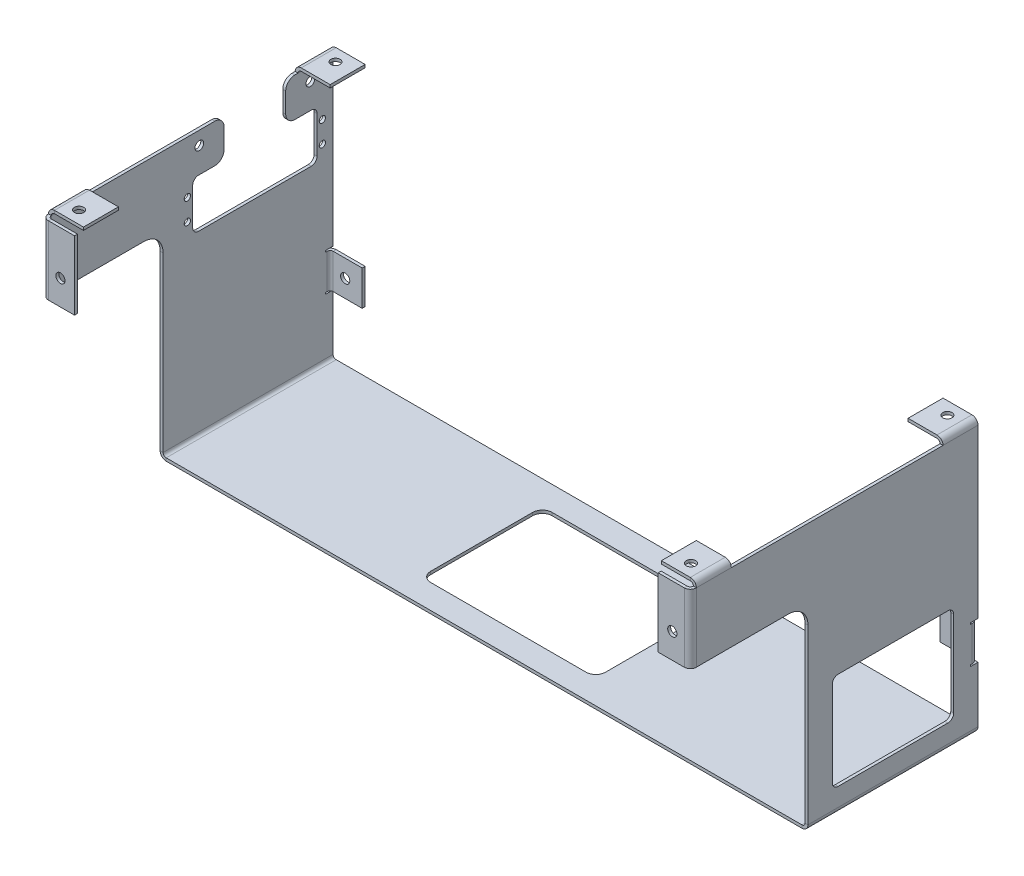
SolidWorks part; units mm, degrees
note: The reader was unsure of these and kept them because the rebuilt part matched: flange length of "Edge-Flange2", "Edge-Flange3", "Edge-Flange6", "Edge-Flange7", "Edge-Flange8".
material "Low Carbon Steel"
ref_plane "Front Plane" through (0, 0, 0) normal (0, 0, 1) x (1, 0, 0)
ref_plane "Top Plane" through (0, 0, 0) normal (0, 1, 0) x (1, 0, 0)
ref_plane "Right Plane" through (0, 0, 0) normal (1, 0, 0) x (0, 0, -1)
sketch "Sketch1" plane through (0, 0, 0) normal (1, 0, 0) x (0, 0, -1)
  line L0 (-175, 198) -> (-290, 198)
  line L1 (0, 0) -> (-175, 0)
  line L2 (0, 0) -> (0, 275)
  line L3 (0, 275) -> (-290, 275)
  line L4 (-175, 0) -> (-175, 198)
  line L5 (-290, 198) -> (-290, 275)
  dimension "D1" = 275
  dimension "D2" = 175
  dimension "D3" = 115
  dimension "D4" = 77
base flange "Base-Flange1" sketch "Sketch1" thickness 3.0378 reverse thickness direction no parameters "D1"=3.175
edge flange "Edge-Flange2" sketch "Sketch16" flange angle 90 flange length 667 flange position bend outside bend radius 3.175 thickness 3.0378 relief rectangular parameters "D6"=10
sketch "Sketch16" plane through (0, 0, 0) normal (0, -1, 0) x (0, 0, -1)
  line L0 (-175, 0) -> (0, 0) construction
  line L1 (-175, 0) -> (0, 0)
  line L2 (-175, 0) -> (-175, 663.9622)
  line L3 (-175, 663.9622) -> (0, 663.9622)
  line L4 (0, 663.9622) -> (0, 0)
bend "EdgeBend3" bend radius 3.175 bend angle 90 parameters "D5"=3
edge flange "Edge-Flange3" sketch "Sketch19" flange angle 90 flange length 281.2128 flange position material inside bend radius 3.175 thickness 3.0378 relief rectangular parameters "D6"=10
sketch "Sketch19" plane through (663.9622, -3.175, 0) normal (1, 0, 0) x (0, 0, -1)
  line L0 (0, 0) -> (-175, 0) construction
  line L1 (0, 0) -> (-175, 0)
  line L2 (-175, 0) -> (-175, 201.175)
  line L3 (-290, 278.175) -> (0, 278.175)
  line L4 (0, 278.175) -> (0, 0)
  line L5 (-175, 201.175) -> (-290, 201.175)
  line L6 (-290, 201.175) -> (-290, 278.175)
  line L7 (0, 278.175) -> (-290, 278.175) construction
  line L8 (-290, 278.175) -> (-290, 201.175) construction
bend "EdgeBend4" bend radius 3.175 bend angle 90 parameters "D5"=4
fillet "Fillet1" radius 20 2 edges at (-1.5189, 198, 175) (662.4432, 198, 175)
edge flange "Edge-Flange6" sketch "Sketch36" flange profiles "Sketch36", "Sketch37" flange angle 90 flange length 36 flange position material inside bend radius 3.175 thickness 3.0378 relief rectangular parameters "D6"=10, "D8"=1
sketch "Sketch36" plane through (0, 275, 0) normal (0, 1, 0) x (0, 0, 1)
  line L0 (0, 0) -> (290, 0) construction
  line L1 (0, 0) -> (290, 0)
  line L2 (0, 0) -> (0, 32.9622)
  line L3 (0, 32.9622) -> (290, 32.9622)
  line L4 (290, 32.9622) -> (290, 0)
sketch "Sketch37" plane through (660.9243, 275, 0) normal (0, 1, 0) x (0, 0, -1)
  line L0 (0, 0) -> (-290, 0) construction
  line L1 (0, 0) -> (-290, 0)
  line L2 (-290, 0) -> (-290, 32.9622)
  line L3 (-290, 32.9622) -> (0, 32.9622)
  line L4 (0, 32.9622) -> (0, 0)
bend "EdgeBend9" bend radius 3.175 bend angle 90 parameters "D5"=5
bend "EdgeBend10" bend radius 3.175 bend angle 90 parameters "D5"=6
sketch "Sketch38" plane through (663.9622, 0, 0) normal (1, 0, 0) x (0, 0, -1)
  line L0 (0, 268.7872) -> (-290, 268.7872) construction
  line L1 (-254, 268.7872) -> (-36, 268.7872)
  line L2 (-254, 268.7872) -> (-254, 275)
  line L3 (-254, 275) -> (-36, 275)
  line L4 (-36, 268.7872) -> (-36, 275)
  line L5 (0, 275) -> (-290, 275) construction
  line L7 (-290, 268.7872) -> (-290, 198) construction
  line L8 (0, 0) -> (0, 268.7872) construction
  dimension "D1" = 36
  dimension "D2" = 36
extrude "Cut-Extrude1" cut sketch "Sketch38" against normal through all
edge flange "Edge-Flange7" sketch "Sketch43" flange profiles "Sketch43", "Sketch44" flange angle 90 flange length 36 flange position material inside bend radius 3.175 thickness 3.0378 relief rectangular parameters "D6"=10, "D8"=1
sketch "Sketch43" plane through (0, 0, 0) normal (0, 0, -1) x (0, 1, 0)
  line L0 (0, 0) -> (268.7872, 0) construction
  line L1 (59, 0) -> (95, 0)
  line L2 (59, 0) -> (59, 32.9622)
  line L3 (59, 32.9622) -> (95, 32.9622)
  line L4 (95, 32.9622) -> (95, 0)
  line L5 (275, 32.9622) -> (275, 3.175) construction
  dimension "D1" = 36
  dimension "D2" = 180
sketch "Sketch44" plane through (660.9243, 0, 0) normal (0, 0, -1) x (0, -1, 0)
  line L0 (0, 0) -> (-268.7872, 0) construction
  line L1 (-59, 0) -> (-95, 0)
  line L2 (-95, 0) -> (-95, 32.9622)
  line L3 (-95, 32.9622) -> (-59, 32.9622)
  line L4 (-59, 32.9622) -> (-59, 0)
  line L5 (-95, 627.9622) -> (-95, 660.9243) construction
  line L6 (-59, 660.9243) -> (-59, 627.9622) construction
bend "EdgeBend11" bend radius 3.175 bend angle 90 parameters "D5"=7
bend "EdgeBend12" bend radius 3.175 bend angle 90 parameters "D5"=8
edge flange "Edge-Flange8" sketch "Sketch57" flange profiles "Sketch57", "Sketch58" flange angle 90 flange length 33 flange position bend outside bend radius 3.175 thickness 3.0378 relief rectangular parameters "D6"=10, "D8"=1
sketch "Sketch57" plane through (0, 0, 290) normal (0, 0, 1) x (0, -1, 0)
  line L2 (-268.7872, 0) -> (-268.7872, 29.9622)
  line L3 (-268.7872, 29.9622) -> (-198, 29.9622)
  line L4 (-198, 29.9622) -> (-198, 0)
  line L7 (-268.7872, 0) -> (-198, 0) construction
  line L8 (-268.7872, 0) -> (-198, 0)
sketch "Sketch58" plane through (660.9243, 0, 290) normal (0, 0, 1) x (0, 1, 0)
  line L0 (268.7872, 0) -> (198, 0) construction
  line L1 (268.7872, 0) -> (198, 0)
  line L2 (198, 0) -> (198, 29.9622)
  line L3 (198, 29.9622) -> (268.7872, 29.9622)
  line L4 (268.7872, 29.9622) -> (268.7872, 0)
bend "EdgeBend13" bend radius 3.175 bend angle 90 parameters "D5"=9
bend "EdgeBend14" bend radius 3.175 bend angle 90 parameters "D5"=10
hole_wizard "Ø9.5 (9.5) Diameter Hole1" positions "Sketch45" profile "Sketch46" hole size "Ø9.5" standard "Peddi DIN" end condition up to next
sketch "Sketch45" plane through (0, 275, 0) normal (0, 1, 0) x (1, 0, 0)
  line L0 (645.4622, -13) -> (645.4622, -277) construction
  line L1 (645.4622, -277) -> (15.4622, -277) construction
  line L2 (15.4622, -277) -> (15.4622, -13) construction
  line L3 (15.4622, -13) -> (645.4622, -13) construction
  line L5 (330.4622, 0) -> (330.4622, -13) construction
  line L6 (3.175, 0) -> (657.7493, 0) construction
  line L8 (32.9622, -36) -> (32.9622, -254) construction
  line L10 (32.9622, -145) -> (15.4622, -145) construction
  point P0 (15.4622, -13)
  point P2 (15.4622, -277)
  point P4 (645.4622, -277)
  point P6 (645.4622, -13)
  dimension "D1" = 630
  dimension "D2" = 264
sketch "Sketch46" plane through (15.4622, 275, 13) normal (1, 0, 0) x (0, 0, 1)
  line L0 (0, 0) -> (0, 3.0378)
  line L1 (0, 3.0378) -> (4.75, 3.0378)
  line L2 (4.75, 3.0378) -> (4.75, 0)
  line L5 (4.75, 0) -> (0, 0)
  line L11 (0, -6.35) -> (0, 107.95) construction
  dimension "Thru Hole Dia." = 9.5
  dimension "Thru Hole Depth" = 3.0378
hole_wizard "Ø9.5 (9.5) Diameter Hole2" positions "Sketch47" profile "Sketch48" hole size "Ø9.5" standard "Peddi DIN" end condition up to next
sketch "Sketch47" plane through (0, 0, 0) normal (0, 0, -1) x (-1, 0, 0)
  line L0 (-15.4622, 77) -> (-645.4622, 77) construction
  line L2 (-330.4622, -3.175) -> (-330.4622, 77) construction
  line L3 (-3.175, -3.175) -> (-657.7493, -3.175) construction
  line L5 (-32.9622, 275) -> (-3.175, 275) construction
  point P0 (-645.4622, 77)
  point P2 (-15.4622, 77)
  dimension "D1" = 630
  dimension "D2" = 198
sketch "Sketch48" plane through (645.4622, 77, 0) normal (1, 0, 0) x (0, 1, 0)
  line L0 (0, 0) -> (0, 3.0378)
  line L1 (0, 3.0378) -> (4.75, 3.0378)
  line L2 (4.75, 3.0378) -> (4.75, 0)
  line L5 (4.75, 0) -> (0, 0)
  line L11 (0, -6.35) -> (0, 107.95) construction
  dimension "Thru Hole Dia." = 9.5
  dimension "Thru Hole Depth" = 3.0378
sketch "Sketch49" plane through (660.9243, 0, 0) normal (-1, 0, 0) x (0, 0, 1)
  line L0 (175, 178) -> (175, 0) construction
  line L1 (144, 118.7872) -> (31, 118.7872)
  line L2 (150, 112.7872) -> (150, 24.7872)
  line L3 (144, 18.7872) -> (31, 18.7872)
  line L4 (25, 112.7872) -> (25, 24.7872)
  line L5 (0, 96.5189) -> (0, 268.7872) construction
  line L6 (0, -6.2128) -> (175, -6.2128) construction
  arc A0 (31, 18.7872) -> (25, 24.7872) centre (31, 24.7872) cw
  arc A1 (150, 24.7872) -> (144, 18.7872) centre (144, 24.7872) cw
  arc A2 (144, 118.7872) -> (150, 112.7872) centre (144, 112.7872) cw
  arc A3 (31, 118.7872) -> (25, 112.7872) centre (31, 112.7872) ccw
  dimension "D6" = 6
  dimension "D1" = 125
  dimension "D2" = 100
  dimension "D3" = 25
  dimension "D4" = 25
  dimension "D5" = 25
extrude "Cut-Extrude2" cut sketch "Sketch49" against normal through all
hole_wizard "M5 Clearance Hole1" positions "Sketch50" profile "Sketch51" hole size "M5" standard "Peddi DIN" end condition up to next
sketch "Sketch50" plane through (-3.0378, 0, 0) normal (-1, 0, 0) x (0, 0, 1)
  line L0 (11.05, 215) -> (150.05, 215) construction
  line L1 (150.05, 215) -> (150.05, 193) construction
  line L2 (150.05, 193) -> (11.05, 193) construction
  line L3 (11.05, 193) -> (11.05, 215) construction
  line L6 (0, 95) -> (0, 59) construction
  line L7 (36, 275) -> (0, 275) construction
  point P0 (11.05, 215)
  point P2 (11.05, 193)
  point P4 (150.05, 215)
  point P6 (150.05, 193)
  dimension "D1" = 139
  dimension "D2" = 22
  dimension "D3" = 60
  dimension "D4" = 11.05
sketch "Sketch51" plane through (-3.0378, 215, 11.05) normal (0, 1, 0) x (0, 0, 1)
  line L0 (0, 0) -> (0, 3.0378)
  line L1 (0, 3.0378) -> (3.25, 3.0378)
  line L2 (3.25, 3.0378) -> (3.25, 0)
  line L5 (3.25, 0) -> (0, 0)
  line L11 (0, -6.35) -> (0, 107.95) construction
  dimension "Thru Hole Dia." = 6.5
  dimension "Thru Hole Depth" = 3.0378
sketch "Sketch52" plane through (-3.0378, 0, 0) normal (-1, 0, 0) x (0, 0, 1)
  line L0 (11.05, 215) -> (11.05, 193) construction
  line L1 (22.55, 229) -> (138.55, 229)
  line L2 (16.55, 223) -> (16.55, 185)
  line L3 (22.55, 179) -> (138.55, 179)
  line L4 (144.55, 223) -> (144.55, 185)
  line L5 (16.55, 204) -> (11.05, 204) construction
  line L6 (150.05, 215) -> (150.05, 193) construction
  line L7 (150.05, 204) -> (144.55, 204) construction
  arc A0 (138.55, 229) -> (144.55, 223) centre (138.55, 223) cw
  arc A1 (138.55, 179) -> (144.55, 185) centre (138.55, 185) ccw
  arc A2 (16.55, 185) -> (22.55, 179) centre (22.55, 185) ccw
  arc A3 (22.55, 229) -> (16.55, 223) centre (22.55, 223) ccw
  dimension "D3" = 6
  dimension "D1" = 50
  dimension "D2" = 128
extrude "Cut-Extrude3" cut sketch "Sketch52" against normal up to next
hole_wizard "Ø9.5 (9.5) Diameter Hole3" positions "Sketch59" profile "Sketch60" hole size "Ø9.5" standard "Peddi DIN" end condition up to next
sketch "Sketch59" plane through (0, 0, 296.2128) normal (0, 0, 1) x (1, 0, 0)
  line L0 (15.4622, 223.7872) -> (645.4622, 223.7872) construction
  line L2 (657.7493, -6.2128) -> (3.175, -6.2128) construction
  line L3 (330.4622, 223.7872) -> (330.4622, -6.2128) construction
  point P0 (645.4622, 223.7872)
  point P2 (15.4622, 223.7872)
  dimension "D1" = 230
  dimension "D2" = 630
sketch "Sketch60" plane through (645.4622, 223.7872, 296.2128) normal (1, 0, 0) x (0, -1, 0)
  line L0 (0, 0) -> (0, 3.0378)
  line L1 (0, 3.0378) -> (4.75, 3.0378)
  line L2 (4.75, 3.0378) -> (4.75, 0)
  line L5 (4.75, 0) -> (0, 0)
  line L11 (0, -6.35) -> (0, 107.95) construction
  dimension "Thru Hole Dia." = 9.5
  dimension "Thru Hole Depth" = 3.0378
sketch "Sketch61" plane through (0, -3.175, 0) normal (0, 1, 0) x (1, 0, 0)
  line L0 (3.175, 0) -> (657.7493, 0) construction
  line L1 (250.4622, -25) -> (410.4622, -25)
  line L2 (240.4622, -35) -> (240.4622, -140)
  line L3 (250.4622, -150) -> (410.4622, -150)
  line L4 (420.4622, -35) -> (420.4622, -140)
  line L9 (657.7493, -175) -> (3.175, -175) construction
  line L12 (330.4622, -150) -> (330.4622, -175) construction
  arc A4 (410.4622, -150) -> (420.4622, -140) centre (410.4622, -140) ccw
  arc A5 (240.4622, -140) -> (250.4622, -150) centre (250.4622, -140) ccw
  arc A6 (250.4622, -25) -> (240.4622, -35) centre (250.4622, -35) ccw
  arc A7 (410.4622, -25) -> (420.4622, -35) centre (410.4622, -35) cw
  dimension "D5" = 10
  dimension "D1" = 180
  dimension "D2" = 25
  dimension "D3" = 25
  dimension "D4" = 125
extrude "Cut-Extrude4" cut sketch "Sketch61" against normal through all
sketch "Sketch62" plane through (-3.0378, 0, 0) normal (-1, 0, 0) x (0, 0, 1)
  line L0 (254, 268.7872) -> (36, 268.7872) construction
  line L1 (48.8, 268.7872) -> (112.3, 268.7872)
  line L2 (48.8, 268.7872) -> (48.8, 229)
  line L3 (48.8, 229) -> (112.3, 229)
  line L4 (112.3, 268.7872) -> (112.3, 229)
  line L5 (138.55, 229) -> (22.55, 229) construction
  line L6 (80.55, 179) -> (80.55, 229) construction
  line L7 (22.55, 179) -> (138.55, 179) construction
  dimension "D1" = 63.5
extrude "Cut-Extrude5" cut sketch "Sketch62" against normal up to next normal cut yes
fillet "Fillet2" radius 9.525 4 edges at (-1.5189, 268.7872, 112.3) (-1.5189, 229, 112.3) (-1.5189, 229, 48.8) (-1.5189, 268.7872, 48.8)
hole_wizard "M8 Clearance Hole1" positions "Sketch63" profile "Sketch64" hole size "M8" standard "Peddi DIN" end condition up to next
sketch "Sketch63" plane through (-3.0378, 0, 0) normal (-1, 0, 0) x (0, 0, 1)
  circle A0 centre (11.05, 215) radius 3.25 construction
  point P0 (23.4, 255.05)
  point P2 (137.7, 255.05)
  dimension "D1" = 114.3
  dimension "D2" = 12.35
  dimension "D3" = 40.05
sketch "Sketch64" plane through (-3.0378, 255.05, 23.4) normal (0, 1, 0) x (0, 0, 1)
  line L0 (0, 0) -> (0, 3.0378)
  line L1 (0, 3.0378) -> (4.5, 3.0378)
  line L2 (4.5, 3.0378) -> (4.5, 0)
  line L5 (4.5, 0) -> (0, 0)
  line L11 (0, -6.35) -> (0, 107.95) construction
  dimension "Thru Hole Dia." = 9
  dimension "Thru Hole Depth" = 3.0378
other "Freeze***"
sketch "Bend-Lines1" [suppressed] plane through (0, 0, 0) normal (0, 1, 0) x (1, 0, 0)
sketch "Bounding-Box1" [suppressed] plane through (0, 0, 0) normal (0, 1, 0) x (1, 0, 0)
sheet metal parameters "Sheet-Metal1" thickness 3.0378 parameters "D1"=3.175
flat pattern "Flat-Pattern1" [suppressed]
sketch "Bend-Lines2" plane through (0, 0, 0) normal (0, 1, 0) x (1, 0, 0)
sketch "Bounding-Box2" [suppressed] plane through (0, 0, 0) normal (0, 1, 0) x (1, 0, 0)
sheet metal parameters "Sheet-Metal3" thickness 3.0378 parameters "D1"=3.175
flat pattern "Flat-Pattern1" [suppressed]
sketch "Bend-Lines2"
sketch "Bounding-Box2" [suppressed] plane through (0, 0, 0) normal (0, 1, 0) x (1, 0, 0)
bend of the flat pattern "Flatten-<EdgeBend3>1"
sheet metal parameters "Sheet-Metal4" thickness 3.0378 parameters "D1"=3.175
flat pattern "Flat-Pattern1" [suppressed]
sketch "Bend-Lines2" plane through (0, 0, 0) normal (0, 1, 0) x (1, 0, 0)
sketch "Bounding-Box2" [suppressed] plane through (0, 0, 0) normal (0, 1, 0) x (1, 0, 0)
bend of the flat pattern "Flatten-<EdgeBend3>1"
bend of the flat pattern "Flatten-<EdgeBend4>1"
sheet metal parameters "Sheet-Metal7" thickness 3.0378 parameters "D1"=3.175
flat pattern "Flat-Pattern1" [suppressed]
sketch "Bend-Lines2" plane through (0, 0, 0) normal (0, 1, 0) x (1, 0, 0)
sketch "Bounding-Box2" [suppressed] plane through (0, 0, 0) normal (0, 1, 0) x (1, 0, 0)
bend of the flat pattern "Flatten-<EdgeBend3>1"
bend of the flat pattern "Flatten-<EdgeBend4>1"
bend of the flat pattern "Flatten-<EdgeBend9>1"
bend of the flat pattern "Flatten-<EdgeBend10>1"
sheet metal parameters "Sheet-Metal8" thickness 3.0378 parameters "D1"=3.175
flat pattern "Flat-Pattern1" [suppressed]
sketch "Bend-Lines2" plane through (0, 0, 0) normal (0, 1, 0) x (1, 0, 0)
sketch "Bounding-Box2" [suppressed] plane through (0, 0, 0) normal (0, 1, 0) x (1, 0, 0)
bend of the flat pattern "Flatten-<EdgeBend3>1"
bend of the flat pattern "Flatten-<EdgeBend4>1"
bend of the flat pattern "Flatten-<EdgeBend9>1"
bend of the flat pattern "Flatten-<EdgeBend10>1"
sheet metal parameters "Sheet-Metal9" thickness 3.0378 parameters "D1"=3.175
flat pattern "Flat-Pattern1" [suppressed]
sketch "Bend-Lines2" plane through (0, 0, 0) normal (0, 1, 0) x (1, 0, 0)
sketch "Bounding-Box2" [suppressed] plane through (0, 0, 0) normal (0, 1, 0) x (1, 0, 0)
bend of the flat pattern "Flatten-<EdgeBend3>1"
bend of the flat pattern "Flatten-<EdgeBend4>1"
bend of the flat pattern "Flatten-<EdgeBend9>1"
bend of the flat pattern "Flatten-<EdgeBend10>1"
bend of the flat pattern "Flatten-<EdgeBend11>1"
bend of the flat pattern "Flatten-<EdgeBend12>1"
sheet metal parameters "Sheet-Metal10" thickness 3.0378 parameters "D1"=3.175
flat pattern "Flat-Pattern1" [suppressed]
sketch "Bend-Lines2" plane through (0, 0, 0) normal (0, 1, 0) x (1, 0, 0)
sketch "Bounding-Box2" [suppressed] plane through (0, 0, 0) normal (0, 1, 0) x (1, 0, 0)
bend of the flat pattern "Flatten-<EdgeBend3>1"
bend of the flat pattern "Flatten-<EdgeBend4>1"
bend of the flat pattern "Flatten-<EdgeBend9>1"
bend of the flat pattern "Flatten-<EdgeBend10>1"
bend of the flat pattern "Flatten-<EdgeBend11>1"
bend of the flat pattern "Flatten-<EdgeBend12>1"
bend of the flat pattern "Flatten-<EdgeBend13>2"
bend of the flat pattern "Flatten-<EdgeBend14>2"
sheet metal parameters "Sheet-Metal11" thickness 3.0378 parameters "D1"=3.175
flat pattern "Flat-Pattern1" [suppressed]
sketch "Bend-Lines2" plane through (0, 0, 0) normal (0, 1, 0) x (1, 0, 0)
sketch "Bounding-Box2" [suppressed] plane through (0, 0, 0) normal (0, 1, 0) x (1, 0, 0)
bend of the flat pattern "Flatten-<EdgeBend3>1"
bend of the flat pattern "Flatten-<EdgeBend4>1"
bend of the flat pattern "Flatten-<EdgeBend9>1"
bend of the flat pattern "Flatten-<EdgeBend10>1"
bend of the flat pattern "Flatten-<EdgeBend11>1"
bend of the flat pattern "Flatten-<EdgeBend12>1"
bend of the flat pattern "Flatten-<EdgeBend13>3"
bend of the flat pattern "Flatten-<EdgeBend14>3"
sheet metal parameters "Sheet-Metal12" thickness 3.0378 parameters "D1"=3.175
flat pattern "Flat-Pattern1" [suppressed]
sketch "Bend-Lines2" plane through (0, 0, 0) normal (0, 1, 0) x (1, 0, 0)
sketch "Bounding-Box2" [suppressed] plane through (0, 0, 0) normal (0, 1, 0) x (1, 0, 0)
bend of the flat pattern "Flatten-<EdgeBend3>1"
bend of the flat pattern "Flatten-<EdgeBend4>1"
bend of the flat pattern "Flatten-<EdgeBend9>1"
bend of the flat pattern "Flatten-<EdgeBend10>1"
bend of the flat pattern "Flatten-<EdgeBend11>1"
bend of the flat pattern "Flatten-<EdgeBend12>1"
bend of the flat pattern "Flatten-<EdgeBend13>4"
bend of the flat pattern "Flatten-<EdgeBend14>4"
sheet metal parameters "Sheet-Metal13" thickness 3.0378 parameters "D1"=3.175
flat pattern "Flat-Pattern1" [suppressed]
sketch "Bend-Lines2" plane through (0, 0, 0) normal (0, 1, 0) x (1, 0, 0)
sketch "Bounding-Box2" [suppressed] plane through (0, 0, 0) normal (0, 1, 0) x (1, 0, 0)
bend of the flat pattern "Flatten-<EdgeBend3>1"
bend of the flat pattern "Flatten-<EdgeBend4>1"
bend of the flat pattern "Flatten-<EdgeBend9>1"
bend of the flat pattern "Flatten-<EdgeBend10>1"
bend of the flat pattern "Flatten-<EdgeBend11>1"
bend of the flat pattern "Flatten-<EdgeBend12>1"
bend of the flat pattern "Flatten-<EdgeBend13>5"
bend of the flat pattern "Flatten-<EdgeBend14>5"
sheet metal parameters "Sheet-Metal14" thickness 3.0378 parameters "D1"=3.175
flat pattern "Flat-Pattern1" [suppressed]
sketch "Bend-Lines2" plane through (0, 0, 0) normal (0, 1, 0) x (1, 0, 0)
sketch "Bounding-Box2" [suppressed] plane through (0, 0, 0) normal (0, 1, 0) x (1, 0, 0)
bend of the flat pattern "Flatten-<EdgeBend3>1"
bend of the flat pattern "Flatten-<EdgeBend4>1"
bend of the flat pattern "Flatten-<EdgeBend9>1"
bend of the flat pattern "Flatten-<EdgeBend10>1"
bend of the flat pattern "Flatten-<EdgeBend11>1"
bend of the flat pattern "Flatten-<EdgeBend12>1"
bend of the flat pattern "Flatten-<EdgeBend13>6"
bend of the flat pattern "Flatten-<EdgeBend14>6"
sheet metal parameters "Sheet-Metal15" thickness 3.0378 parameters "D1"=3.175
flat pattern "Flat-Pattern1" [suppressed]
sketch "Bend-Lines2" plane through (0, 0, 0) normal (0, 1, 0) x (1, 0, 0)
sketch "Bounding-Box2" [suppressed] plane through (0, 0, 0) normal (0, 1, 0) x (1, 0, 0)
bend of the flat pattern "Flatten-<EdgeBend3>1"
bend of the flat pattern "Flatten-<EdgeBend4>1"
bend of the flat pattern "Flatten-<EdgeBend9>1"
bend of the flat pattern "Flatten-<EdgeBend10>1"
bend of the flat pattern "Flatten-<EdgeBend11>1"
bend of the flat pattern "Flatten-<EdgeBend12>1"
bend of the flat pattern "Flatten-<EdgeBend13>1"
bend of the flat pattern "Flatten-<EdgeBend14>1"
sheet metal parameters "Sheet-Metal16" thickness 3.0378 parameters "D1"=3.175
flat pattern "Flat-Pattern1"
sketch "Bend-Lines2" plane through (0, 0, 0) normal (1, 0, 0) x (0, 0, -1)
  line L0 (-293.448, -866.3663) -> (-293.448, -937.1535) construction
  line L1 (-293.448, 268.7872) -> (-293.448, 198) construction
  line L2 (-2.7648, -763.3663) -> (-2.7648, -727.3663) construction
  line L3 (-2.7648, 59) -> (-2.7648, 95) construction
  line L4 (-290, -940.6015) -> (0, -940.6015) construction
  line L5 (0, 272.2352) -> (-290, 272.2352) construction
  line L6 (-175, -664.9183) -> (0, -664.9183) construction
  line L7 (-175, -3.448) -> (0, -3.448) construction
  line L8 (-293.448, -866.3663) -> (-293.448, -937.1535) construction
  line L9 (-293.448, 268.7872) -> (-293.448, 198) construction
  line L10 (-2.7648, -763.3663) -> (-2.7648, -727.3663) construction
  line L11 (-2.7648, 59) -> (-2.7648, 95) construction
  line L12 (-290, -940.6015) -> (-254, -940.6015) construction
  line L13 (-36, -940.6015) -> (0, -940.6015) construction
  line L14 (0, 272.2352) -> (-36, 272.2352) construction
  line L15 (-254, 272.2352) -> (-290, 272.2352) construction
  line L16 (-175, -664.9183) -> (0, -664.9183) construction
  line L17 (-175, -3.448) -> (0, -3.448) construction
sketch3d "Bounding-Box2" [suppressed]
  line L0 (-323.6832, 305.4703, 0) -> (-323.6832, -973.8367, 0) construction
  line L1 (30.4703, 305.4703, 0) -> (30.4703, -973.8367, 0) construction
  line L2 (-323.6832, 305.4703, 0) -> (30.4703, 305.4703, 0) construction
  line L3 (-323.6832, -973.8367, 0) -> (30.4703, -973.8367, 0) construction
bend of the flat pattern "Flatten-<EdgeBend3>1"
bend of the flat pattern "Flatten-<EdgeBend4>1"
bend of the flat pattern "Flatten-<EdgeBend9>1"
bend of the flat pattern "Flatten-<EdgeBend10>1"
bend of the flat pattern "Flatten-<EdgeBend11>1"
bend of the flat pattern "Flatten-<EdgeBend12>1"
bend of the flat pattern "Flatten-<EdgeBend13>6"
bend of the flat pattern "Flatten-<EdgeBend14>6"
sheet metal parameters "Sheet-Metal17" thickness 3.0378 parameters "D1"=3.175
flat pattern "Flat-Pattern1"
sketch "Bend-Lines2" plane through (0, 0, 0) normal (1, 0, 0) x (0, 0, -1)
  line L0 (-293.448, -866.3663) -> (-293.448, -937.1535) construction
  line L1 (-293.448, 268.7872) -> (-293.448, 198) construction
  line L2 (-2.7648, -763.3663) -> (-2.7648, -727.3663) construction
  line L3 (-2.7648, 59) -> (-2.7648, 95) construction
  line L4 (-290, -940.6015) -> (0, -940.6015) construction
  line L5 (0, 272.2352) -> (-290, 272.2352) construction
  line L6 (-175, -664.9183) -> (0, -664.9183) construction
  line L7 (-175, -3.448) -> (0, -3.448) construction
  line L8 (-293.448, -866.3663) -> (-293.448, -937.1535) construction
  line L9 (-293.448, 268.7872) -> (-293.448, 198) construction
  line L10 (-2.7648, -763.3663) -> (-2.7648, -727.3663) construction
  line L11 (-2.7648, 59) -> (-2.7648, 95) construction
  line L12 (-290, -940.6015) -> (-254, -940.6015) construction
  line L13 (-36, -940.6015) -> (0, -940.6015) construction
  line L14 (0, 272.2352) -> (-36, 272.2352) construction
  line L15 (-254, 272.2352) -> (-290, 272.2352) construction
  line L16 (-175, -664.9183) -> (0, -664.9183) construction
  line L17 (-175, -3.448) -> (0, -3.448) construction
sketch3d "Bounding-Box2" [suppressed]
  line L0 (30.4703, 305.4703, 0) -> (30.4703, -973.8367, 0) construction
  line L1 (-323.6832, 305.4703, 0) -> (-323.6832, -973.8367, 0) construction
  line L2 (30.4703, 305.4703, 0) -> (-323.6832, 305.4703, 0) construction
  line L3 (30.4703, -973.8367, 0) -> (-323.6832, -973.8367, 0) construction
bend of the flat pattern "Flatten-<EdgeBend3>1"
bend of the flat pattern "Flatten-<EdgeBend4>1"
bend of the flat pattern "Flatten-<EdgeBend9>1"
bend of the flat pattern "Flatten-<EdgeBend10>1"
bend of the flat pattern "Flatten-<EdgeBend11>1"
bend of the flat pattern "Flatten-<EdgeBend12>1"
bend of the flat pattern "Flatten-<EdgeBend13>6"
bend of the flat pattern "Flatten-<EdgeBend14>6"
sheet metal parameters "Sheet-Metal18" thickness 3.0378 parameters "D1"=3.175
flat pattern "Flat-Pattern1"
sketch "Bend-Lines2" plane through (0, 0, 0) normal (1, 0, 0) x (0, 0, -1)
  line L0 (-293.448, -866.3663) -> (-293.448, -937.1535) construction
  line L1 (-293.448, 268.7872) -> (-293.448, 198) construction
  line L2 (-2.7648, -763.3663) -> (-2.7648, -727.3663) construction
  line L3 (-2.7648, 59) -> (-2.7648, 95) construction
  line L4 (-290, -940.6015) -> (0, -940.6015) construction
  line L5 (0, 272.2352) -> (-290, 272.2352) construction
  line L6 (-175, -664.9183) -> (0, -664.9183) construction
  line L7 (-175, -3.448) -> (0, -3.448) construction
  line L8 (-293.448, -866.3663) -> (-293.448, -937.1535) construction
  line L9 (-293.448, 268.7872) -> (-293.448, 198) construction
  line L10 (-2.7648, -763.3663) -> (-2.7648, -727.3663) construction
  line L11 (-2.7648, 59) -> (-2.7648, 95) construction
  line L12 (-290, -940.6015) -> (-254, -940.6015) construction
  line L13 (-36, -940.6015) -> (0, -940.6015) construction
  line L14 (0, 272.2352) -> (-36, 272.2352) construction
  line L15 (-254, 272.2352) -> (-290, 272.2352) construction
  line L16 (-175, -664.9183) -> (0, -664.9183) construction
  line L17 (-175, -3.448) -> (0, -3.448) construction
sketch3d "Bounding-Box2" [suppressed]
  line L0 (30.4703, 305.4703, 0) -> (30.4703, -973.8367, 0) construction
  line L1 (-323.6832, 305.4703, 0) -> (-323.6832, -973.8367, 0) construction
  line L2 (30.4703, 305.4703, 0) -> (-323.6832, 305.4703, 0) construction
  line L3 (30.4703, -973.8367, 0) -> (-323.6832, -973.8367, 0) construction
bend of the flat pattern "Flatten-<EdgeBend3>1"
bend of the flat pattern "Flatten-<EdgeBend4>1"
bend of the flat pattern "Flatten-<EdgeBend9>1"
bend of the flat pattern "Flatten-<EdgeBend10>1"
bend of the flat pattern "Flatten-<EdgeBend11>1"
bend of the flat pattern "Flatten-<EdgeBend12>1"
bend of the flat pattern "Flatten-<EdgeBend13>6"
bend of the flat pattern "Flatten-<EdgeBend14>6"
sheet metal parameters "Sheet-Metal19" thickness 3.0378 parameters "D1"=3.175
flat pattern "Flat-Pattern1"
sketch "Bend-Lines2" plane through (0, 0, 0) normal (1, 0, 0) x (0, 0, -1)
  line L0 (-293.448, -866.3663) -> (-293.448, -937.1535) construction
  line L1 (-293.448, 268.7872) -> (-293.448, 198) construction
  line L2 (-2.7648, -763.3663) -> (-2.7648, -727.3663) construction
  line L3 (-2.7648, 59) -> (-2.7648, 95) construction
  line L4 (-290, -940.6015) -> (0, -940.6015) construction
  line L5 (-254, 272.2352) -> (-36, 272.2352) construction
  line L6 (-175, -664.9183) -> (0, -664.9183) construction
  line L7 (-175, -3.448) -> (0, -3.448) construction
  line L8 (-293.448, -866.3663) -> (-293.448, -937.1535) construction
  line L9 (-293.448, 268.7872) -> (-293.448, 198) construction
  line L10 (-2.7648, -763.3663) -> (-2.7648, -727.3663) construction
  line L11 (-2.7648, 59) -> (-2.7648, 95) construction
  line L12 (-290, -940.6015) -> (-254, -940.6015) construction
  line L13 (-36, -940.6015) -> (0, -940.6015) construction
  line L14 (-254, 272.2352) -> (-290, 272.2352) construction
  line L15 (0, 272.2352) -> (-36, 272.2352) construction
  line L16 (-175, -664.9183) -> (0, -664.9183) construction
  line L17 (-175, -3.448) -> (0, -3.448) construction
sketch3d "Bounding-Box2" [suppressed]
  line L0 (30.4703, 305.4703, 0) -> (30.4703, -973.8367, 0) construction
  line L1 (-323.6832, 305.4703, 0) -> (-323.6832, -973.8367, 0) construction
  line L2 (30.4703, 305.4703, 0) -> (-323.6832, 305.4703, 0) construction
  line L3 (30.4703, -973.8367, 0) -> (-323.6832, -973.8367, 0) construction
bend of the flat pattern "Flatten-<EdgeBend3>1"
bend of the flat pattern "Flatten-<EdgeBend4>1"
bend of the flat pattern "Flatten-<EdgeBend9>1"
bend of the flat pattern "Flatten-<EdgeBend10>1"
bend of the flat pattern "Flatten-<EdgeBend11>1"
bend of the flat pattern "Flatten-<EdgeBend12>1"
bend of the flat pattern "Flatten-<EdgeBend13>6"
bend of the flat pattern "Flatten-<EdgeBend14>6"
